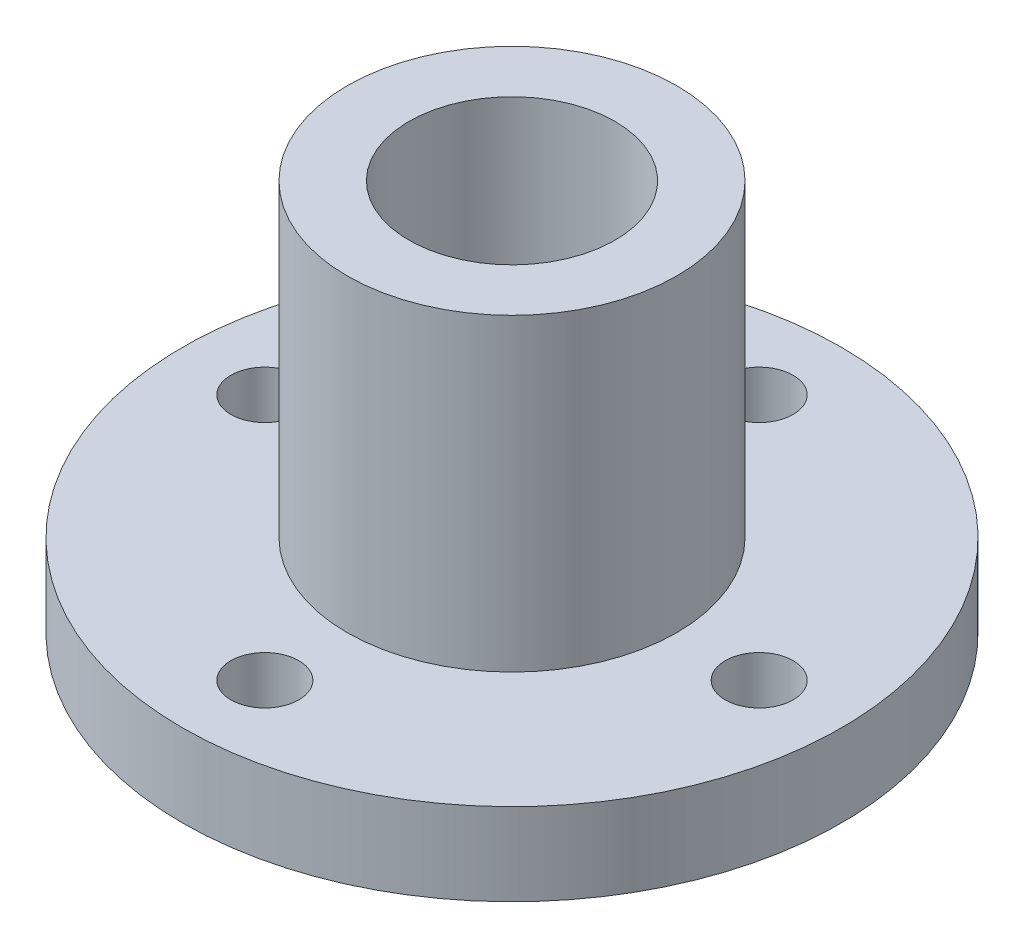
SolidWorks part; units mm, degrees
material "Brass"
ref_plane "Front Plane" through (0, 0, 0) normal (0, 0, 1) x (1, 0, 0)
ref_plane "Top Plane" through (0, 0, 0) normal (0, 1, 0) x (1, 0, 0)
ref_plane "Right Plane" through (0, 0, 0) normal (1, 0, 0) x (0, 0, -1)
sketch "Sketch1" plane through (0, 0, 0) normal (0, 0, 1) x (1, 0, 0)
  line L0 (0, 0) -> (0, 23.4843) construction
  line L1 (0, 0) -> (-33.509, 0) construction
  line L2 (-5, 0) -> (-5, 19)
  line L3 (-5, 19) -> (-8, 19)
  line L4 (-8, 19) -> (-8, 4)
  line L5 (-8, 4) -> (-16, 4)
  line L6 (-16, 4) -> (-16, 0)
  line L7 (-16, 0) -> (-5, 0)
  dimension "D1" = 19
  dimension "D2" = 4
  dimension "D3" = 10
  dimension "D4" = 16
  dimension "D5" = 32
revolve "Revolve1" add sketch "Sketch1" angle 360 about L0
sketch "Sketch2" plane through (0, 0, 0) normal (0, -1, 0) x (1, 0, 0)
  circle A0 centre (0, 0) radius 12 construction
  point P3 (0, 12)
  point P4 (12, 0)
  point P5 (0, -12)
  point P6 (-12, 0)
  dimension "D1" = 24
hole_wizard "Ø3.3 (3.3) Diameter Hole1" positions "Sketch3" profile "Sketch4" hole size "Ø3.3" standard "ANSI Metric" end condition through all
sketch "Sketch3" plane through (0, 0, 0) normal (0, -1, 0) x (-1, 0, 0)
  point P0 (-12, 0)
  point P3 (0, 12)
  point P6 (12, 0)
  point P9 (0, -12)
sketch "Sketch4" plane through (12, 0, 0) normal (1, 0, 0) x (0, 0, -1)
  line L0 (0, 0) -> (0, 19)
  line L1 (0, 19) -> (1.65, 19)
  line L2 (1.65, 19) -> (1.65, 0)
  line L5 (1.65, 0) -> (0, 0)
  line L11 (0, -6.35) -> (0, 107.95) construction
  dimension "Thru Hole Dia." = 3.3
  dimension "Thru Hole Depth" = 19
